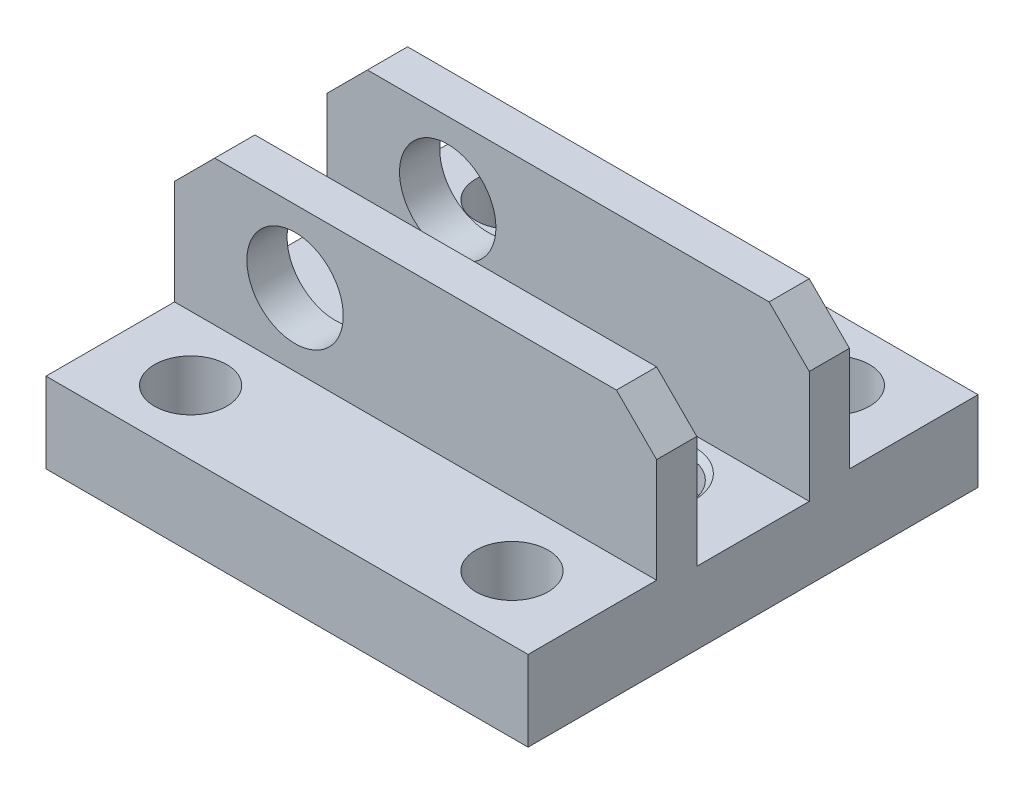
SolidWorks part; units mm, degrees
ref_plane "Front Plane" through (0, 0, 0) normal (0, 0, 1) x (1, 0, 0)
ref_plane "Top Plane" through (0, 0, 0) normal (0, 1, 0) x (1, 0, 0)
ref_plane "Right Plane" through (0, 0, 0) normal (1, 0, 0) x (0, 0, -1)
ref_plane "Plane1" through (0, 0, 0) normal (0, 0, 1) x (1, 0, 0)
sketch "Sketch1" plane through (0, 0, 0) normal (0, 0, 1) x (1, 0, 0)
  line L0 (0, 11.5) -> (0, 0)
  line L1 (0, 0) -> (30, 0)
  line L2 (30, 0) -> (30, 11.5)
  line L3 (30, 11.5) -> (27.5, 14)
  line L4 (27.5, 14) -> (2.5, 14)
  line L5 (2.5, 14) -> (0, 11.5)
extrude "Boss-Extrude1" add sketch "Sketch1" against normal blind 14 and the other way blind 14
ref_plane "Plane2" through (0, 0, 0) normal (0, 0, 1) x (1, 0, 0)
sketch "Sketch2" plane through (0, 0, 0) normal (0, 0, 1) x (1, 0, 0)
  circle A0 centre (7.5, 9.5) radius 3
extrude "Cut-Extrude1" cut sketch "Sketch2" against normal blind 14 and the other way blind 14
ref_plane "Plane3" through (0, 0, 0) normal (0, 0, 1) x (1, 0, 0)
sketch "Sketch3" plane through (0, 0, 0) normal (0, 0, 1) x (1, 0, 0)
  line L0 (0, 14) -> (0, 4.5)
  line L1 (0, 4.5) -> (30, 4.5)
  line L2 (30, 4.5) -> (30, 14)
  line L3 (30, 14) -> (0, 14)
extrude "Cut-Extrude2" cut sketch "Sketch3" against normal blind 3.5 and the other way blind 3.5
ref_plane "Plane4" through (0, 0, 0) normal (0, 0, 1) x (1, 0, 0)
sketch "Sketch4" plane through (0, 0, 0) normal (0, 0, 1) x (1, 0, 0)
  line L0 (23.5, 4.5) -> (26.3536, 4.5)
  line L1 (26.3536, 4.5) -> (26, 4.1464)
  line L2 (26, 4.1464) -> (26, 2.5)
  line L3 (26, 2.5) -> (23.5, 2.5)
  line L4 (23.5, 2.5) -> (23.5, 4.5)
  line L5 (23.5, 2.5) -> (23.5, 4.5) construction
revolve "Cut-Revolve1" cut sketch "Sketch4" angle 360 about L5 reverse direction yes
ref_plane "Plane5" through (0, 0, 0) normal (1, 0, 0) x (0, 0, -1)
sketch "Sketch5" plane through (0, 0, 0) normal (1, 0, 0) x (0, 0, -1)
  line L0 (-28, 26) -> (-28, -2)
  line L1 (-28, -2) -> (28, -2)
  line L2 (28, -2) -> (28, 26)
  line L3 (28, 26) -> (-28, 26)
  line L4 (-14, 5) -> (-14, 0)
  line L5 (-14, 0) -> (14, 0)
  line L6 (14, 0) -> (14, 5)
  line L7 (14, 5) -> (6, 5)
  line L8 (6, 5) -> (6, 14)
  line L9 (6, 14) -> (-6, 14)
  line L10 (-6, 14) -> (-6, 5)
  line L11 (-6, 5) -> (-14, 5)
extrude "Cut-Extrude3" cut sketch "Sketch5" along normal blind 30
ref_plane "Plane6" through (0, 0, 0) normal (0, 1, 0) x (1, 0, 0)
sketch "Sketch6" plane through (0, 0, 0) normal (0, 1, 0) x (1, 0, 0)
  circle A0 centre (5, -10) radius 2.25
extrude "Cut-Extrude4" cut sketch "Sketch6" along normal blind 5
ref_plane "Plane7" through (0, 0, 0) normal (0, 1, 0) x (1, 0, 0)
sketch "Sketch7" plane through (0, 0, 0) normal (0, 1, 0) x (1, 0, 0)
  circle A0 centre (25, 10) radius 2.25
extrude "Cut-Extrude5" cut sketch "Sketch7" along normal blind 5
ref_plane "Plane8" through (0, 0, 0) normal (0, 1, 0) x (1, 0, 0)
sketch "Sketch8" plane through (0, 0, 0) normal (0, 1, 0) x (1, 0, 0)
  circle A0 centre (25, -10) radius 2.25
extrude "Cut-Extrude6" cut sketch "Sketch8" along normal blind 5
ref_plane "Plane9" through (0, 0, 0) normal (0, 1, 0) x (1, 0, 0)
sketch "Sketch9" plane through (0, 0, 0) normal (0, 1, 0) x (1, 0, 0)
  circle A0 centre (5, 10) radius 2.25
extrude "Cut-Extrude7" cut sketch "Sketch9" along normal blind 5
